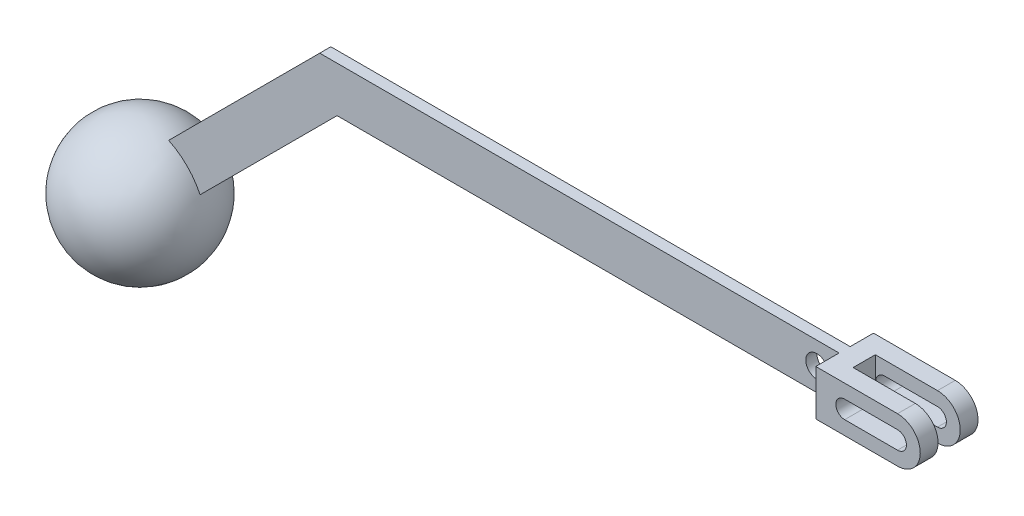
SolidWorks part; units mm, degrees
ref_plane "前视基准面" through (0, 0, 0) normal (0, 0, 1) x (1, 0, 0)
ref_plane "上视基准面" through (0, 0, 0) normal (0, 1, 0) x (1, 0, 0)
ref_plane "右视基准面" through (0, 0, 0) normal (1, 0, 0) x (0, 0, -1)
sketch "草图1" plane through (0, 0, 0) normal (0, 0, 1) x (1, 0, 0)
  line L0 (-52.6473, 0) -> (29.1954, 0) construction
  line L1 (-52.6473, 10.2348) -> (29.1954, 10.2348)
  line L2 (29.1954, 4) -> (-15.8046, 4)
  line L3 (29.1954, -10.2348) -> (-70.8046, -10.2348)
  line L4 (-52.6473, 10.2348) -> (-138.1153, 10.2348)
  line L5 (-15.8046, -4) -> (29.1954, -4)
  line L6 (-138.1153, 10.2348) -> (-260.8046, 10.2348)
  line L7 (-160.8046, -10.2348) -> (-70.8046, -10.2348)
  line L8 (-260.8046, 10.2348) -> (-260.8046, -10.2348)
  line L9 (-260.8046, -10.2348) -> (-160.8046, -10.2348)
  arc A1 (29.1954, -10.2348) -> (29.1954, 10.2348) centre (29.1954, 0) ccw
  arc A3 (29.1954, -4) -> (29.1954, 4) centre (29.1954, 0) ccw
  arc A4 (-15.8046, 4) -> (-15.8046, -4) centre (-15.8046, 0) ccw
  dimension "D1" = 100
  dimension "D2" = 100
  dimension "D3" = 4
  dimension "D4" = 8
  dimension "D5" = 45
  dimension "D6" = 90
extrude "凸台-拉伸1" add sketch "草图1" along normal blind 5
sketch "草图2" plane through (-260.8046, 0, 0) normal (-1, 0, 0) x (0, 0, 1)
  line L0 (-10.9909, 0) -> (19.2385, 0) construction
  line L1 (-17.5, 20) -> (22.5, 20)
  line L2 (-17.5, 20) -> (-17.5, -20)
  line L3 (-17.5, -20) -> (22.5, -20)
  line L4 (22.5, 20) -> (22.5, -20)
  line L5 (2.5, 11.2641) -> (2.5, -15.107) construction
  dimension "D1" = 40
  dimension "D2" = 40
  dimension "D3" = 20
  dimension "D4" = 20
extrude "凸台-拉伸2" add sketch "草图2" along normal blind 40
fillet "圆角1" radius 10 12 edges at (-260.8046, -20, 2.5) (-260.8046, 20, 2.5) (-300.8046, 20, 2.5) (-300.8046, -20, 2.5) (-280.8046, 20, -17.5) (-300.8046, 0, -17.5) (-280.8046, -20, -17.5) (-260.8046, 0, -17.5) (-280.8046, -20, 22.5) (-300.8046, 0, 22.5) (-280.8046, 20, 22.5) (-260.8046, 0, 22.5)
fillet "圆角2" radius 2 8 edges at (-260.8073, 10.2348, 2.5) (-260.8046, 0, 5) (-260.8073, -10.2348, 2.5) (-260.8046, 0, 0) (-260.8053, -10.1174, 5) (-260.8053, -10.1174, 0) (-260.8053, 10.1174, 0) (-260.8053, 10.1174, 5)
sketch "草图3" plane through (0, 0, 5) normal (0, 0, 1) x (1, 0, 0)
  line L0 (-28.8289, 10.2348) -> (-28.8289, -10.2348)
  line L1 (29.1954, 10.2348) -> (-258.8069, 10.2348) construction
  line L2 (-258.8069, -10.2348) -> (29.1954, -10.2348) construction
  line L3 (-28.8289, -10.2348) -> (29.1954, -10.2348)
  line L4 (29.1954, 10.2348) -> (-28.8289, 10.2348)
  line L5 (-15.8046, 4) -> (29.1954, 4)
  line L6 (-15.8046, -4) -> (29.1954, -4)
  arc A0 (29.1954, -10.2348) -> (29.1954, 10.2348) centre (29.1954, 0) ccw
  arc A1 (-15.8046, 4) -> (-15.8046, -4) centre (-15.8046, 0) ccw
  arc A2 (29.1954, -4) -> (29.1954, 4) centre (29.1954, 0) ccw
extrude "凸台-拉伸3" add sketch "草图3" along normal blind 20
ref_plane "基准面4" through (0, 0, 2.5) normal (0, 0, 1) x (1, 0, 0)
mirror "镜向1" about plane through (0, 0, 2.5) normal (0, 0, 1) of "凸台-拉伸3"
ref_plane "基准面5" through (60, 0, 0) normal (1, 0, 0) x (0, 0, -1)
sketch "草图4" plane through (60, 0, 0) normal (1, 0, 0) x (0, 0, -1)
  line L0 (-2.5, 24.0567) -> (-2.5, -27.5399) construction
  line L1 (-7, 10) -> (-12.5, 10) construction
  line L2 (-7.5, 10) -> (2.5, 10)
  line L3 (-7.5, 10) -> (-7.5, -10)
  line L4 (-7.5, -10) -> (2.5, -10)
  line L5 (2.5, 10) -> (2.5, -10)
  line L6 (2, -10) -> (7.5, -10) construction
  dimension "D1" = 10
  dimension "D2" = 5
extrude "切除-拉伸1" cut sketch "草图4" against normal blind 80
sketch "草图5" plane through (60, 0, 0) normal (1, 0, 0) x (0, 0, -1)
  line L0 (2.5, 10) -> (2.5, -10) construction
  line L1 (-15.5, 21.3005) -> (-30.2943, 21.3005)
  line L2 (-15.5, 21.3005) -> (-15.5, -26.781)
  line L3 (-15.5, -26.781) -> (-30.2943, -26.781)
  line L4 (-30.2943, 21.3005) -> (-30.2943, -26.781)
  line L5 (10.5, 22.9279) -> (34.6887, 22.9279)
  line L6 (10.5, 22.9279) -> (10.5, -25.0057)
  line L7 (10.5, -25.0057) -> (34.6887, -25.0057)
  line L8 (34.6887, 22.9279) -> (34.6887, -25.0057)
  line L9 (-7.5, -10) -> (-7.5, 10) construction
  dimension "D1" = 8
  dimension "D2" = 8
extrude "切除-拉伸2" cut sketch "草图5" against normal up to surface (88.8289 mm away) up to face at (-28.8289, 0, 15)
sketch "草图7" plane through (0, 0, 5) normal (0, 0, 1) x (1, 0, 0)
  line L0 (-28.8289, 10.2348) -> (-28.8289, -10.2348) construction
  circle A0 centre (-38.8289, 0) radius 5
  dimension "D1" = 10
  dimension "D2" = 10
extrude "切除-拉伸4" cut sketch "草图7" against normal through all
sketch "草图8" plane through (-20, 0, 0) normal (1, 0, 0) x (0, 0, -1)
  line L1 (-7.5, 19.816) -> (2.5, 19.816)
  line L2 (-7.5, 19.816) -> (-7.5, -21.6444)
  line L3 (-7.5, -21.6444) -> (2.5, -21.6444)
  line L4 (2.5, 19.816) -> (2.5, -21.6444)
extrude "切除-拉伸5" cut sketch "草图8" along normal blind 111
sketch "草图9" plane through (0, 0, 15.5) normal (0, 0, 1) x (1, 0, 0)
  circle A0 centre (15, 0) radius 4
  circle A1 centre (15, 0) radius 10.2348
  dimension "D1" = 15
extrude "凸台-拉伸4" add sketch "草图9" against normal up to surface (26 mm away) up to face at (6.6954, 0, -10.5)
sketch "草图10" plane through (0, 0, 15.5) normal (0, 0, 1) x (1, 0, 0)
  line L0 (15, 10.2348) -> (49.8866, 10.2348)
  line L1 (49.8866, 10.2348) -> (49.8866, -12.372)
  line L2 (49.8866, -12.372) -> (15, -10.2348)
  arc A0 (15, -10.2348) -> (15, 10.2348) centre (15, 0) ccw
extrude "切除-拉伸6" cut sketch "草图10" against normal through all
sketch "草图11" plane through (0, 0, 15.5) normal (0, 0, 1) x (1, 0, 0)
  line L0 (5.5792, 4) -> (15, 4)
  line L1 (15, 4) -> (15, -4)
  line L2 (15, -4) -> (2.5046, -4)
  line L3 (2.5046, -4) -> (2.5046, 4)
  line L4 (-15.8046, 4) -> (5.5792, 4) construction
  line L5 (2.5046, 4) -> (5.5792, 4)
  circle A0 centre (15, 0) radius 4 construction
extrude "切除-拉伸7" cut sketch "草图11" against normal through all
sketch "草图12" plane through (-20, 0, 0) normal (1, 0, 0) x (0, 0, -1)
  line L1 (-7.5, 10.2348) -> (2.5, 10.2348)
  line L2 (-7.5, 10.2348) -> (-7.5, -25.4619)
  line L3 (-7.5, -25.4619) -> (2.5, -25.4619)
  line L4 (2.5, 10.2348) -> (2.5, -25.4619)
  point P5 (0, 0)
extrude "切除-拉伸8" cut sketch "草图12" along normal blind 162
sketch "草图13" plane through (0, 0, 15.5) normal (0, 0, 1) x (1, 0, 0)
  circle A0 centre (8, 0) radius 4
  circle A1 centre (8, 0) radius 10.2348
  dimension "D1" = 8
extrude "凸台-拉伸5" add sketch "草图13" against normal up to surface (26 mm away) up to face at (-0.4023, 0, -10.5)
sketch "草图14" plane through (0, 0, 15.5) normal (0, 0, 1) x (1, 0, 0)
  line L0 (8, 10.2348) -> (37.0054, 10.2348)
  line L1 (37.0054, 10.2348) -> (37.0054, -19.761)
  line L2 (37.0054, -19.761) -> (8, -10.2348)
  arc A0 (8, -10.2348) -> (8, 10.2348) centre (8, 0) ccw
extrude "切除-拉伸9" cut sketch "草图14" against normal through all
sketch "草图15" plane through (0, 0, 15.5) normal (0, 0, 1) x (1, 0, 0)
  line L0 (-1.4208, 4) -> (8, 4)
  line L1 (8, 4) -> (8, -4)
  line L2 (8, -4) -> (-4.9507, -4)
  line L3 (-1.4208, -4) -> (-15.8046, -4) construction
  line L4 (-4.9507, -4) -> (-4.9507, 4)
  line L5 (-15.8046, 4) -> (-1.4208, 4) construction
  line L6 (-4.9507, 4) -> (-1.4208, 4)
  circle A0 centre (8, 0) radius 4 construction
extrude "切除-拉伸10" cut sketch "草图15" against normal through all
sketch "草图16" plane through (-20, 0, 0) normal (1, 0, 0) x (0, 0, -1)
  line L1 (-7.5, 10.2348) -> (2.5, 10.2348)
  line L2 (-7.5, 10.2348) -> (-7.5, -25.4479)
  line L3 (-7.5, -25.4479) -> (2.5, -25.4479)
  line L4 (2.5, 10.2348) -> (2.5, -25.4479)
  point P5 (0, 0)
extrude "切除-拉伸11" cut sketch "草图16" along normal blind 162
sketch "草图19" plane through (0, 0, 5) normal (0, 0, 1) x (1, 0, 0)
  line L0 (-258.8046, 10) -> (-258.8046, -10) construction
  line L1 (-323.1016, 37.5576) -> (-258.8046, 37.5576)
  line L2 (-323.1016, 37.5576) -> (-323.1016, -42.648)
  line L3 (-323.1016, -42.648) -> (-258.8046, -42.648)
  line L4 (-258.8046, 37.5576) -> (-258.8046, -42.648)
extrude "切除-拉伸12" cut sketch "草图19" against normal mid plane 85
sketch "草图20" plane through (0, 0, 5) normal (0, 0, 1) x (1, 0, 0)
  line L0 (-258.8046, 0) -> (-343.6574, -84.8528) construction
  line L1 (-258.8046, 10.2348) -> (-258.8046, -10.2348) construction
  line L2 (-258.8046, -10.2348) -> (-28.8289, -10.2348) construction
  line L3 (-343.6574, -84.8528) -> (-336.5863, -91.9239)
  line L4 (-343.6574, -84.8528) -> (-350.7285, -77.7817)
  line L5 (-350.7285, -77.7817) -> (-262.7119, 10.2348)
  line L6 (-336.5863, -91.9239) -> (-254.8973, -10.2348)
  line L7 (-258.8046, 10.2348) -> (-262.7119, 10.2348)
  line L8 (-258.8046, 10.2348) -> (-258.8046, -10.2348)
  line L9 (-258.8046, -10.2348) -> (-254.8973, -10.2348)
  dimension "D1" = 120
  dimension "D2" = 135
  dimension "D3" = 10
  dimension "D4" = 10
extrude "凸台-拉伸7" add sketch "草图20" against normal up to surface (5 mm away) up to face at (-33.8289, 0, 0)
sketch "草图21" plane through (0, 0, 5) normal (0, 0, 1) x (1, 0, 0)
  line L0 (-350.7285, -77.7817) -> (-336.5863, -91.9239) construction
  line L1 (-373.6574, -84.8528) -> (-313.6574, -84.8528)
  arc A0 (-313.6574, -84.8528) -> (-373.6574, -84.8528) centre (-343.6574, -84.8528) ccw
  dimension "D1" = 60
revolve "旋转2" add sketch "草图21" angle 360 about L1
